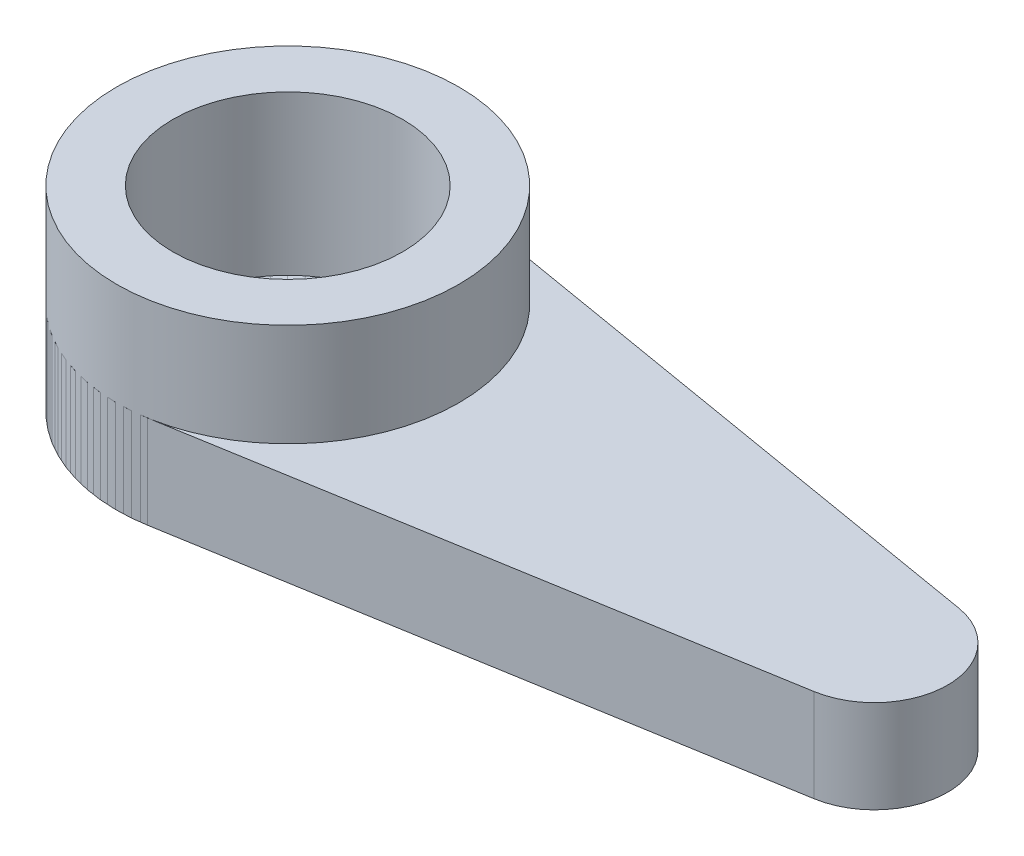
SolidWorks part; units mm, degrees
ref_plane "Front Plane" through (0, 0, 0) normal (0, 0, 1) x (1, 0, 0)
ref_plane "Top Plane" through (0, 0, 0) normal (0, 1, 0) x (1, 0, 0)
ref_plane "Right Plane" through (0, 0, 0) normal (1, 0, 0) x (0, 0, -1)
sketch "Sketch1" plane through (0, 0, 0) normal (0, 1, 0) x (1, 0, 0)
  circle A0 centre (0, 0) radius 3.5
  circle A1 centre (0, 0) radius 1.5
extrude "Boss-Extrude1" add sketch "Sketch1" along normal blind 4
sketch "Sketch2" plane through (0, 0, 0) normal (0, -1, 0) x (1, 0, 0)
  line L0 (-3.5, 0) -> (-3.5, 10.8846) construction
  line L1 (13.5, 0) -> (13.5, 8.8292) construction
  line L2 (0.5833, 3.451) -> (12.25, 1.479)
  line L3 (0, 0) -> (7.4207, 0) construction
  line L4 (0.5833, -3.451) -> (12.25, -1.479)
  arc A0 (0.5833, 3.451) -> (0.5833, -3.451) centre (0, 0) ccw
  arc A1 (12.25, -1.479) -> (12.25, 1.479) centre (12, 0) ccw
  circle A2 centre (0, 0) radius 1.5
  dimension "D1" = 17
extrude "Boss-Extrude2" add sketch "Sketch2" against normal blind 1.9 separate body
sketch "Sketch3" plane through (0, 4, 0) normal (0, 1, 0) x (1, 0, 0)
  circle A0 centre (0, 0) radius 2.35
extrude "Cut-Extrude1" cut sketch "Sketch3" against normal blind 3.25
